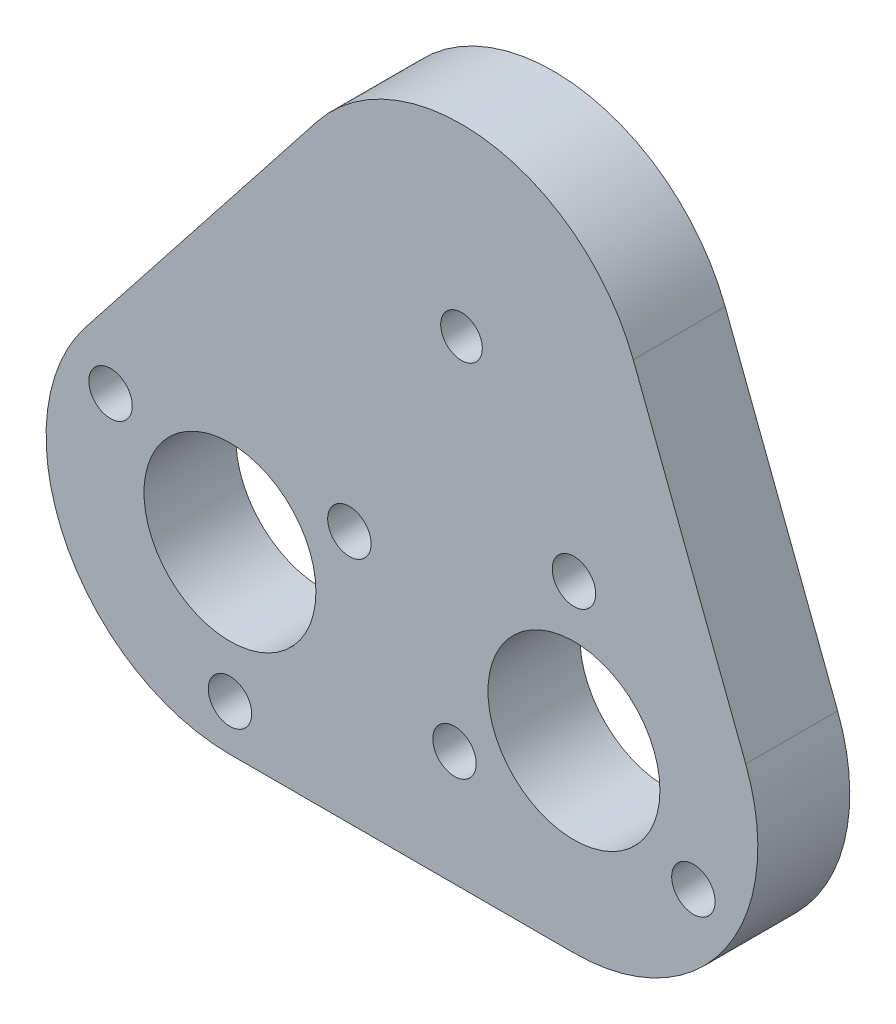
SolidWorks part; units mm, degrees
material "Balsa"
ref_plane "Front Plane" through (0, 0, 0) normal (0, 0, 1) x (1, 0, 0)
ref_plane "Top Plane" through (0, 0, 0) normal (0, 1, 0) x (1, 0, 0)
ref_plane "Right Plane" through (0, 0, 0) normal (1, 0, 0) x (0, 0, -1)
sketch "Sketch1" plane through (0, 0, 0) normal (0, 0, 1) x (1, 0, 0)
  line L0 (0, 0) -> (-15.9905, -20.2933) construction
  line L1 (-15.9905, -20.2933) -> (7.766, -20.2933) construction
  line L2 (7.766, -20.2933) -> (0, 0) construction
  line L9 (-25.9658, -12.4331) -> (-9.9753, 7.8602)
  line L10 (-15.9905, -32.9933) -> (7.766, -32.9933)
  line L11 (11.8611, 4.5391) -> (19.6272, -15.7542)
  circle A0 centre (0, 0) radius 1.4375
  circle A1 centre (-15.9905, -20.2933) radius 5.9375
  circle A2 centre (7.766, -20.2933) radius 5.9375
  circle A6 centre (0, 0) radius 12.7
  circle A7 centre (-15.9905, -20.2933) radius 12.7
  circle A8 centre (7.766, -20.2933) radius 12.7
  point P11 (-2.061, -12.8283)
  point P12 (-4.0601, -15.352)
  point P13 (-1.1359, -15.352)
  dimension "D2" = 25.4
  dimension "D3" = 11.875
  dimension "D6" = 23.7566
  dimension "D10" = 11.875
  dimension "D12" = 2.875
  dimension "D7" = 25.8363
  dimension "D8" = 21.7286
extrude "Boss-Extrude1" add sketch "Sketch1" along normal blind 6.35 contours A8 A6 L9 A7 | A8 A6 A0 | A6 A8 A7 A2 | A8 A7 A1 | A8 A7 L10 | A6 A8 | A7 A8 | A8 L11 A6 region at (-14.1109, -8.0907, 0) region at (-14.3803, -5.1248, 0) region at (1.8558, 12.2019, 0) region at (-4.1122, -30.7724, 0) region at (-3.0027, -14.2511, 0) region at (-4.1122, -20.2933, 0) region at (14.1336, -6.2239, 0) region at (3.883, -10.1467, 0)
sketch "Sketch2" plane through (0, 0, 6.35) normal (0, 0, 1) x (1, 0, 0)
  line L0 (-15.9905, -20.2933) -> (-27.4167, -25.837) construction
  line L1 (7.766, -20.2933) -> (18.2288, -27.4921) construction
  arc A0 (-25.9658, -12.4331) -> (-15.9905, -32.9933) centre (-15.9905, -20.2933) ccw construction
  circle A1 centre (-15.9905, -20.2933) radius 5.9375 construction
  arc A2 (7.766, -32.9933) -> (19.6272, -15.7542) centre (7.766, -20.2933) ccw construction
  point P8 (-21.3325, -22.8851)
ref_plane "Plane1" through (-27.4167, -25.837, 6.35) normal (-0.8997, -0.4365, 0) x (0, 0, 1)
sketch "Sketch8" plane through (0, 0, 6.35) normal (0, 0, 1) x (1, 0, 0)
  circle A0 centre (-15.9905, -20.2933) radius 9.525 construction
  circle A1 centre (7.766, -20.2933) radius 9.525 construction
  circle A2 centre (7.766, -10.7683) radius 1.5
  circle A3 centre (-15.9905, -29.8183) radius 1.5
  circle A4 centre (-24.2394, -15.5308) radius 1.5
  circle A5 centre (-7.7416, -15.5308) radius 1.5
  circle A6 centre (16.0149, -25.0558) radius 1.5
  circle A7 centre (-0.4828, -25.0558) radius 1.5
  point P16 (-15.9905, -20.2933)
  point P22 (7.766, -20.2933)
  dimension "D1" = 19.05
  dimension "D2" = 3
  dimension "D3" = 3
  dimension "D4" = 3
extrude "Cut-Extrude1" cut sketch "Sketch8" against normal through all
